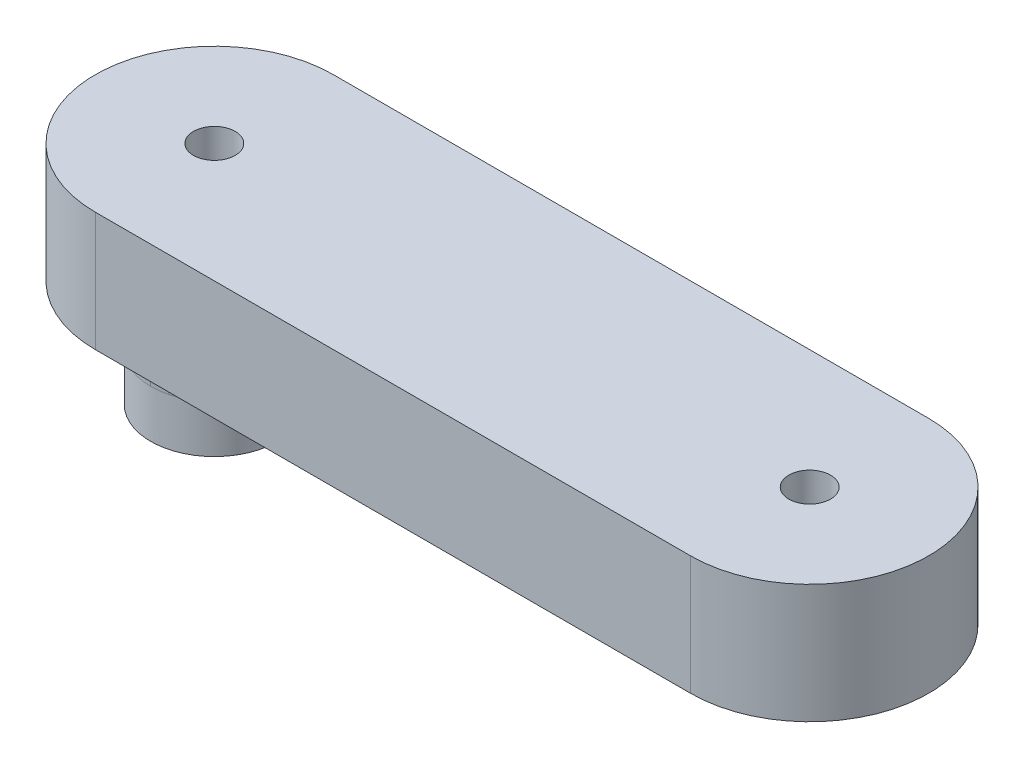
SolidWorks part; units mm, degrees
ref_plane "Front Plane" through (0, 0, 0) normal (0, 0, 1) x (1, 0, 0)
ref_plane "Top Plane" through (0, 0, 0) normal (0, 1, 0) x (1, 0, 0)
ref_plane "Right Plane" through (0, 0, 0) normal (1, 0, 0) x (0, 0, -1)
sketch "Sketch1" plane through (0, 0, 0) normal (0, 1, 0) x (1, 0, 0)
  line L0 (-25, 0) -> (25, 0) construction
  line L1 (-25, 10) -> (25, 10)
  line L2 (-25, -10) -> (25, -10)
  arc A0 (-25, 10) -> (-25, -10) centre (-25, 0) ccw
  arc A1 (25, -10) -> (25, 10) centre (25, 0) ccw
  point P3 (0, 0)
  dimension "D1" = 10
  dimension "D2" = 50
extrude "Boss-Extrude1" add sketch "Sketch1" along normal blind 10
sketch "Sketch2" plane through (0, 10, 0) normal (0, 1, 0) x (1, 0, 0)
  circle A5 centre (25, 0) radius 1.75
  dimension "D1" = 3.5
extrude "Cut-Extrude1" cut sketch "Sketch2" against normal up to next
sketch "Sketch5" plane through (0, 0, 0) normal (0, -1, 0) x (1, 0, 0)
  circle A0 centre (-25, 0) radius 5.35
  dimension "D1" = 10.7
extrude "Boss-Extrude3" add sketch "Sketch5" along normal blind 9
fillet "Fillet1" radius 5 1 edges at (-25, 0, 5.35)
sketch "Sketch6" plane through (0, -9, 0) normal (0, -1, 0) x (-1, 0, 0)
  circle A0 centre (25, 0) radius 1.75
  dimension "D1" = 3.5
extrude "Cut-Extrude2" cut sketch "Sketch6" against normal up to next
equation "\"Length\"= 50mm"
equation "\"Radius\"= 10mm"
equation "\"D1@Sketch1\"= \"Radius\""
equation "\"D2@Sketch1\" = \"Length\""
equation "\"Thick\"= 10mm"
equation "\"D1@Boss-Extrude1\"= \"Thick\""
